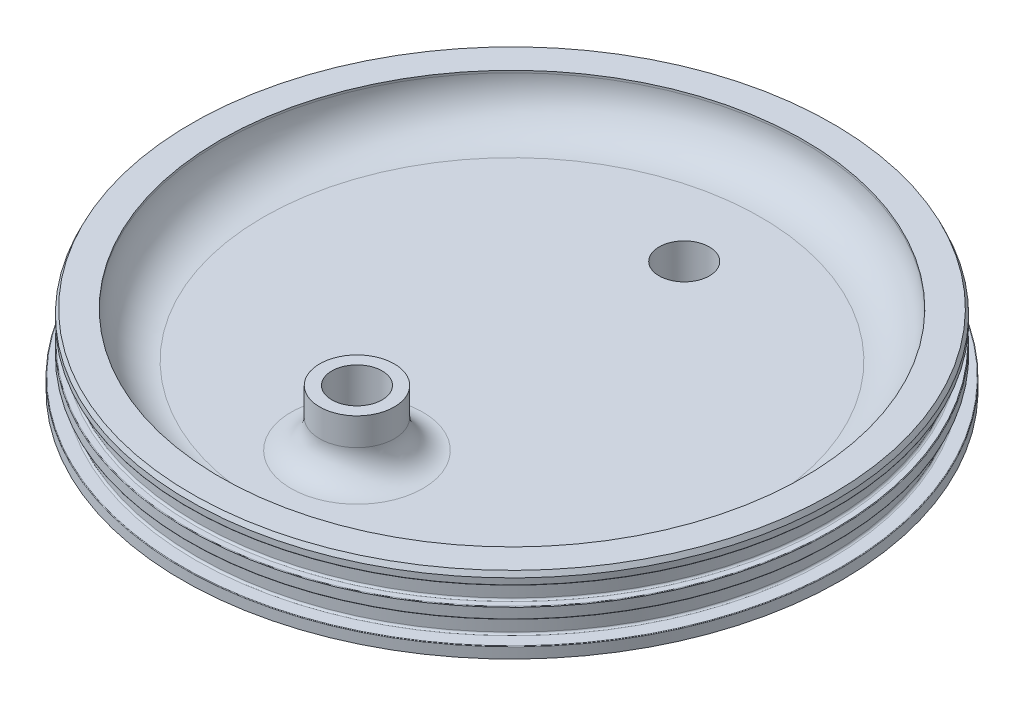
SolidWorks part; units mm, degrees
material "6061-T6 (SS)"
ref_plane "Front Plane" through (0, 0, 0) normal (0, 0, 1) x (1, 0, 0)
ref_plane "Top Plane" through (0, 0, 0) normal (0, 1, 0) x (1, 0, 0)
ref_plane "Right Plane" through (0, 0, 0) normal (1, 0, 0) x (0, 0, -1)
sketch "Sketch1" plane through (0, 0, 0) normal (0, 0, 1) x (1, 0, 0)
  line L0 (0, 48.1922) -> (0, -25.6743) construction
  line L1 (0, 0) -> (72.898, 0)
  line L2 (72.898, 0) -> (72.898, 2.4638)
  line L3 (72.898, 2.4638) -> (69.6468, 2.4638)
  line L4 (69.6468, 2.4638) -> (69.6468, 6.5278)
  line L5 (69.6468, 6.5278) -> (71.4248, 6.5278)
  line L6 (71.4248, 6.5278) -> (71.4248, 8.9916)
  line L7 (71.4248, 8.9916) -> (69.6468, 8.9916)
  line L8 (64.5668, 15.5956) -> (64.5668, 5.588)
  line L9 (64.5668, 5.588) -> (0, 5.588)
  line L10 (0, 5.588) -> (0, 0)
  line L11 (69.6468, 8.9916) -> (69.6468, 13.0556)
  line L12 (69.6468, 13.0556) -> (71.4248, 13.0556)
  line L13 (71.4248, 13.0556) -> (71.4248, 15.5956)
  line L14 (71.4248, 15.5956) -> (64.5668, 15.5956)
  dimension "D2" = 4.064
  dimension "D5" = 5.588
  dimension "D7" = 4.064
  dimension "D4" = 2.4638
  dimension "D8" = 2.54
  dimension "D6" = 5.08
  dimension "D1" = 72.898
  dimension "D9" = 1.778
  dimension "D3" = 69.6468
revolve "Revolve1" add sketch "Sketch1" angle 360 about L0
sketch "Sketch6" plane through (0, 0, 0) normal (0, -1, 0) x (1, 0, 0)
  circle A0 centre (0, 0) radius 66.04
  dimension "D1" = 132.08
extrude "Boss-Extrude1" add sketch "Sketch6" along normal blind 2.54
hole_wizard "Pipe Tap Drill for 1/4 Tap - GN2" positions "Sketch2" profile "Sketch3" hole size "1/4" standard "ANSI Inch" end condition through all
sketch "Sketch2" plane through (0, 5.588, 0) normal (0, 1, 0) x (1, 0, 0)
  point P4 (0, -34.29)
  dimension "D1" = 34.29
sketch "Sketch3" plane through (0, 5.588, 34.29) normal (1, 0, 0) x (0, 0, 1)
  line L0 (0, 0) -> (0, 8.128)
  line L1 (0, 8.128) -> (5.5626, 8.128)
  line L2 (5.5626, 8.128) -> (5.5626, 0)
  line L5 (5.5626, 0) -> (0, 0)
  line L11 (0, -6.35) -> (0, 107.95) construction
  dimension "Thru Hole Dia." = 11.1252
  dimension "Thru Hole Depth" = 8.128
fillet "CNC ID Fillet" radius 0.4064 5 edges at (-69.6468, 6.5278, 0) (-69.6468, 2.4638, 0) (-69.6468, 13.0556, 0) (-69.6468, 8.9916, 0) (66.04, 0, 0)
fillet "CNC OD Fillet" radius 0.127 5 edges at (-71.4248, 6.5278, 0) (-72.898, 2.4638, 0) (66.04, -2.54, 0) (-71.4248, 13.0556, 0) (-71.4248, 8.9916, 0)
chamfer "CNC Chamfers" distance 0.508 angle 65 1 edges at (-71.4248, 15.5956, 0) first distance on face at (-64.5668, 15.5956, 0)
hole_wizard "Pipe Tap Drill for 1/4 Tap - Relief Valve" positions "Sketch13" profile "Sketch14" hole size "1/4" standard "ANSI Inch" end condition through all
sketch "Sketch13" plane through (0, -2.54, 0) normal (0, -1, 0) x (-1, 0, 0)
  point P4 (0, 38.1)
  dimension "D1" = 38.1
sketch "Sketch14" plane through (0, -2.54, -38.1) normal (1, 0, 0) x (0, 0, -1)
  line L0 (0, 0) -> (0, 18.1356)
  line L1 (0, 18.1356) -> (5.5626, 18.1356)
  line L2 (5.5626, 18.1356) -> (5.5626, 0)
  line L5 (5.5626, 0) -> (0, 0)
  line L11 (0, -6.35) -> (0, 107.95) construction
  dimension "Thru Hole Dia." = 11.1252
  dimension "Thru Hole Depth" = 18.1356
sketch "Sketch15" plane through (0, -2.54, 0) normal (0, -1, 0) x (1, 0, 0)
  circle A0 centre (0, 34.29) radius 8.255
  circle A1 centre (0, 34.29) radius 5.5626 construction
  circle A2 centre (0, 34.29) radius 5.5626
  dimension "D1" = 16.51
extrude "Boss-Extrude2" add sketch "Sketch15" against normal blind 12.446 from surface starting at face at (5.5626, 5.588, -38.1)
fillet "Fillet2" radius 6.35 1 edges at (8.255, 5.588, 34.29)
fillet "Fillet3" radius 9.525 1 edges at (-64.5668, 5.588, 0)
sketch "Sketch16" plane through (0, -2.54, 0) normal (0, -1, 0) x (1, 0, 0)
  line L0 (0, 34.29) -> (0, -38.1) construction
  line L1 (25.4, 26.67) -> (-25.4, 26.67) construction
  line L2 (-9.4223, -1.905) -> (9.4223, -1.905) construction
  line L3 (25.4, -30.48) -> (-25.4, -30.48) construction
  text T0 "GN2"
  text T1 "VENT\r\n"
  point P7 (0, 26.67)
  point P14 (0, -1.905)
  dimension "D1" = 50.8
  dimension "D2" = 7.62
equation "\"D3@Sketch1\"=5.484/2"
